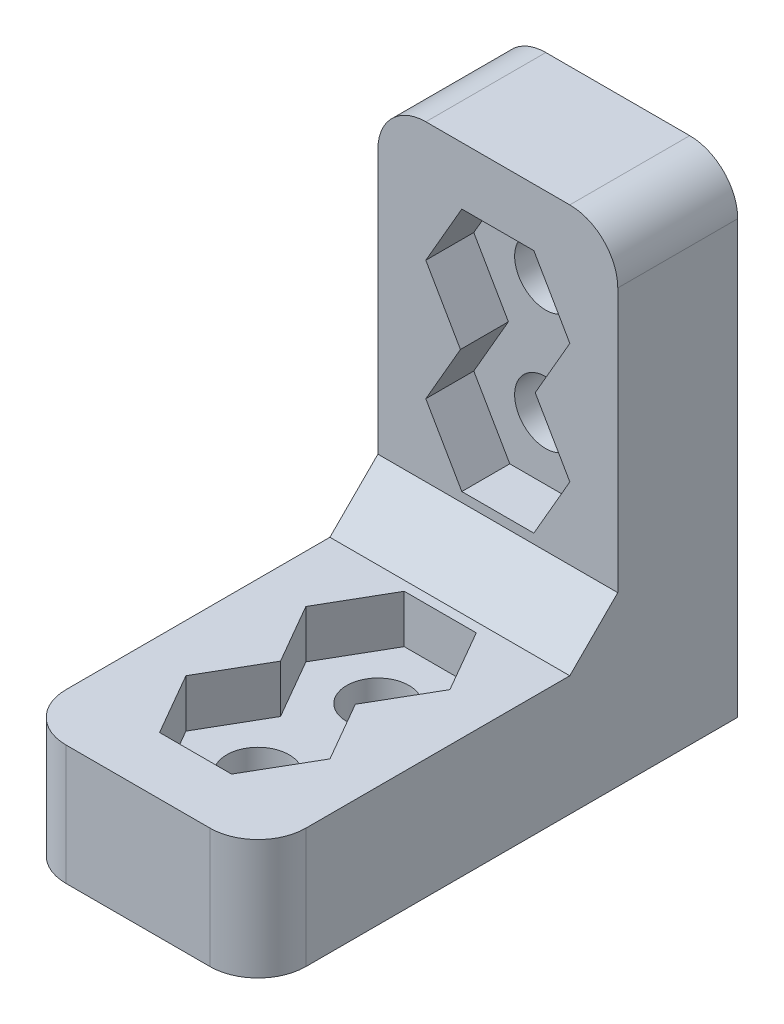
SolidWorks part; units mm, degrees
ref_plane "Front Plane" through (0, 0, 0) normal (0, 0, 1) x (1, 0, 0)
ref_plane "Top Plane" through (0, 0, 0) normal (0, 1, 0) x (1, 0, 0)
ref_plane "Right Plane" through (0, 0, 0) normal (1, 0, 0) x (0, 0, -1)
sketch "Sketch1" plane through (0, 0, 0) normal (1, 0, 0) x (0, 0, -1)
  line L0 (0, 0) -> (0, 19.05)
  line L1 (0, 19.05) -> (6.35, 19.05)
  line L2 (6.35, 19.05) -> (6.35, -6.35)
  line L3 (6.35, -6.35) -> (-19.05, -6.35)
  line L4 (-19.05, -6.35) -> (-19.05, 0)
  line L5 (-19.05, 0) -> (0, 0)
  dimension "D1" = 6.35
  dimension "D2" = 19.05
extrude "Boss-Extrude1" add sketch "Sketch1" along normal blind 6.35 and the other way blind 6.35
sketch "Sketch2" plane through (0, 0, 0) normal (0, 1, 0) x (1, 0, 0)
  line L0 (-6.35, 0) -> (6.35, 0) construction
  line L1 (0, 0) -> (0, -6.35) construction
  line L2 (0, -6.35) -> (0, -12.7) construction
  circle A0 centre (0, -6.35) radius 1.651
  circle A1 centre (0, -12.7) radius 1.651
  dimension "D2" = 3.302
  dimension "D3" = 6.35
  dimension "D4" = 6.35
extrude "Cut-Extrude1" cut sketch "Sketch2" against normal blind 25.4
sketch "Sketch3" plane through (0, 0, 0) normal (0, 1, 0) x (1, 0, 0)
  line L0 (-1.9064, -9.398) -> (-1.9797, -9.525) construction
  line L1 (1.9064, -3.048) -> (-1.9064, -3.048)
  line L2 (-1.9064, -3.048) -> (-3.8128, -6.35)
  line L3 (-3.8128, -6.35) -> (-1.9797, -9.525)
  line L4 (-1.9064, -9.652) -> (1.9064, -9.652) construction
  line L5 (1.9797, -9.525) -> (3.8128, -6.35)
  line L6 (3.8128, -6.35) -> (1.9064, -3.048)
  line L7 (1.9064, -9.398) -> (-1.9064, -9.398) construction
  line L8 (-1.9797, -9.525) -> (-3.8128, -12.7)
  line L9 (-3.8128, -12.7) -> (-1.9064, -16.002)
  line L10 (-1.9064, -16.002) -> (1.9064, -16.002)
  line L11 (1.9064, -16.002) -> (3.8128, -12.7)
  line L12 (3.8128, -12.7) -> (1.9797, -9.525)
  line L13 (-1.9797, -9.525) -> (-1.9064, -9.652) construction
  line L14 (1.9797, -9.525) -> (1.9064, -9.398) construction
  line L15 (1.9064, -9.652) -> (1.9797, -9.525) construction
  circle A0 centre (0, -6.35) radius 3.302 construction
  circle A1 centre (0, -12.7) radius 3.302 construction
  dimension "D1" = 6.604
  dimension "D2" = 6.604
extrude "Cut-Extrude2" cut sketch "Sketch3" against normal blind 2.54
sketch "Sketch4" plane through (0, 0, 0) normal (0, 0, 1) x (1, 0, 0)
  line L0 (0, 0) -> (0, 6.35) construction
  line L1 (0, 6.35) -> (0, 12.7) construction
  circle A0 centre (0, 12.7) radius 1.651
  circle A1 centre (0, 6.35) radius 1.651
  point P7 (0, 6.3641)
  dimension "D1" = 3.302
  dimension "D2" = 6.35
  dimension "D3" = 6.35
extrude "Cut-Extrude3" cut sketch "Sketch4" against normal blind 6.35
sketch "Sketch5" plane through (0, 0, 0) normal (0, 0, 1) x (1, 0, 0)
  line L0 (-1.9064, 9.652) -> (-1.9797, 9.525) construction
  line L1 (1.9064, 16.002) -> (-1.9064, 16.002)
  line L2 (-1.9064, 16.002) -> (-3.8128, 12.7)
  line L3 (-3.8128, 12.7) -> (-1.9797, 9.525)
  line L4 (-1.9064, 9.398) -> (1.9064, 9.398) construction
  line L5 (1.9797, 9.525) -> (3.8128, 12.7)
  line L6 (3.8128, 12.7) -> (1.9064, 16.002)
  line L7 (3.8128, 6.35) -> (1.9797, 9.525)
  line L8 (1.9064, 9.652) -> (-1.9064, 9.652) construction
  line L9 (-1.9797, 9.525) -> (-3.8128, 6.35)
  line L10 (-3.8128, 6.35) -> (-1.9064, 3.048)
  line L11 (-1.9064, 3.048) -> (1.9064, 3.048)
  line L12 (1.9064, 3.048) -> (3.8128, 6.35)
  line L13 (-1.9797, 9.525) -> (-1.9064, 9.398) construction
  line L14 (1.9797, 9.525) -> (1.9064, 9.652) construction
  line L15 (1.9064, 9.398) -> (1.9797, 9.525) construction
  circle A0 centre (0, 12.7) radius 3.302 construction
  circle A1 centre (0, 6.35) radius 3.302 construction
  point P10 (0, 6.35)
  dimension "D1" = 6.604
  dimension "D2" = 6.604
extrude "Cut-Extrude4" cut sketch "Sketch5" against normal blind 2.54
chamfer "Chamfer1" distance 2.54 angle 45 1 edges at (0, 0, 0)
fillet "Fillet1" radius 2.54 4 edges at (-6.35, -3.175, 19.05) (6.35, -3.175, 19.05) (6.35, 19.05, -3.175) (-6.35, 19.05, -3.175)
